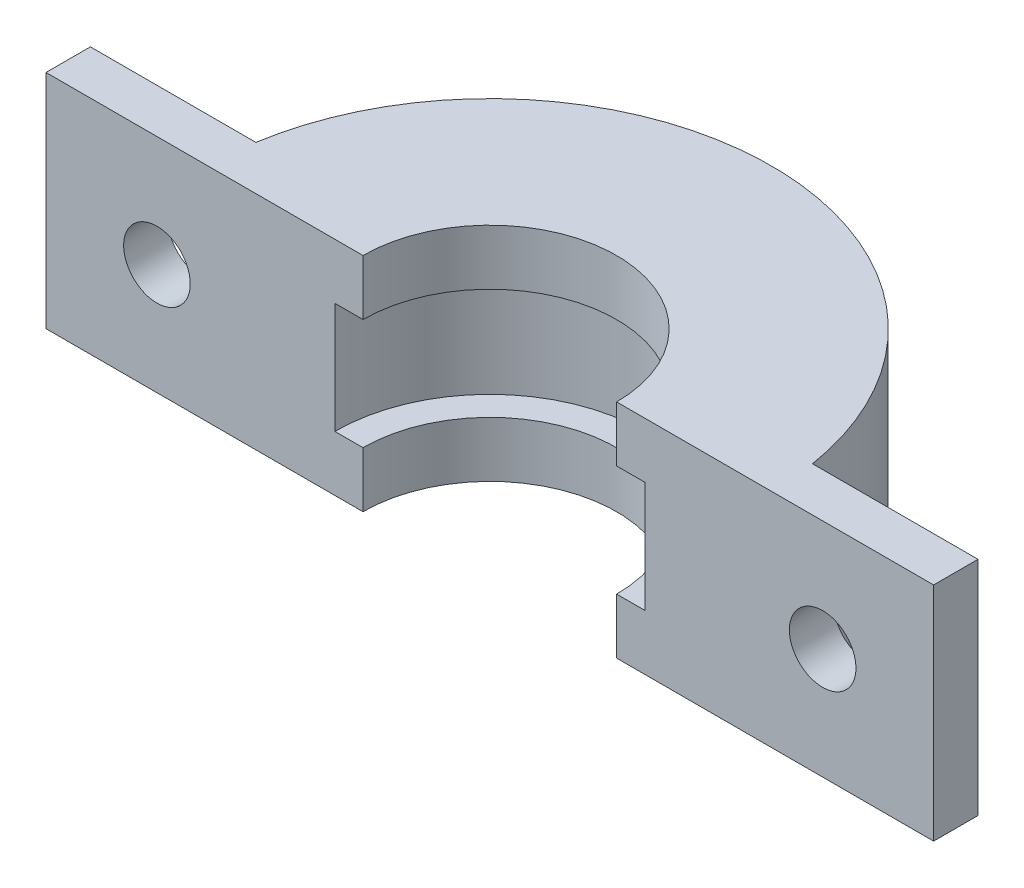
SolidWorks part; units mm, degrees
ref_plane "Front Plane" through (0, 0, 0) normal (0, 0, 1) x (1, 0, 0)
ref_plane "Top Plane" through (0, 0, 0) normal (0, 1, 0) x (1, 0, 0)
ref_plane "Right Plane" through (0, 0, 0) normal (1, 0, 0) x (0, 0, -1)
sketch "Sketch1" plane through (0, 0, 0) normal (0, 1, 0) x (1, 0, 0)
  line L0 (12.7, 0) -> (-12.7, 0)
  circle A0 centre (0, 0) radius 12.7
  circle A1 centre (0, 0) radius 5.715
  point P7 (0, 0)
  dimension "D1" = 25.4
  dimension "D2" = 11.43
extrude "Boss-Extrude1" add sketch "Sketch1" along normal mid plane 10 contours A1 L0 A0 region at (0, 0, -6.1428)
ref_plane "Plane1" through (0, 0, 0) normal (0, 1, 0) x (1, 0, 0)
sketch "Sketch2" plane through (0, 0, 0) normal (0, 1, 0) x (1, 0, 0)
  line L0 (-6.985, 0) -> (6.985, 0)
  circle A0 centre (0, 0) radius 6.985
  dimension "D1" = 13.97
extrude "Cut-Extrude1" cut sketch "Sketch2" against normal mid plane 5 contours L0 A0 region at (0, 0, -2.9645)
sketch "Sketch3" plane through (0, 0, 0) normal (0, 0, 1) x (1, 0, 0)
  line L0 (0, -5) -> (0, 5) construction
  line L1 (11, 5) -> (20, 5)
  line L2 (5.715, 5) -> (-5.715, 5) construction
  line L3 (6.985, 0) -> (-6.985, 0) construction
  line L4 (-11, -5) -> (-20, -5)
  line L5 (-11, -5) -> (-11, 5)
  line L6 (-11, 5) -> (-20, 5)
  line L7 (-20, -5) -> (-20, 5)
  line L8 (-11, -5) -> (-20, 5) construction
  line L9 (-11, 5) -> (-20, -5) construction
  line L10 (20, -5) -> (20, 5)
  line L11 (-5.715, -5) -> (-12.7, -5) construction
  line L12 (11, -5) -> (20, -5)
  line L13 (-12.7, 5) -> (-12.7, -5) construction
  line L18 (11, -5) -> (11, 5)
  circle A2 centre (-15, 0) radius 1.5
  circle A3 centre (15, 0) radius 1.5
  point P0 (-15.5, 0)
  point P4 (0, 0)
  dimension "D2" = 5
  dimension "D4" = 3
  dimension "D1" = 9
  dimension "D3" = 1.7
extrude "Boss-Extrude2" add sketch "Sketch3" against normal blind 2
